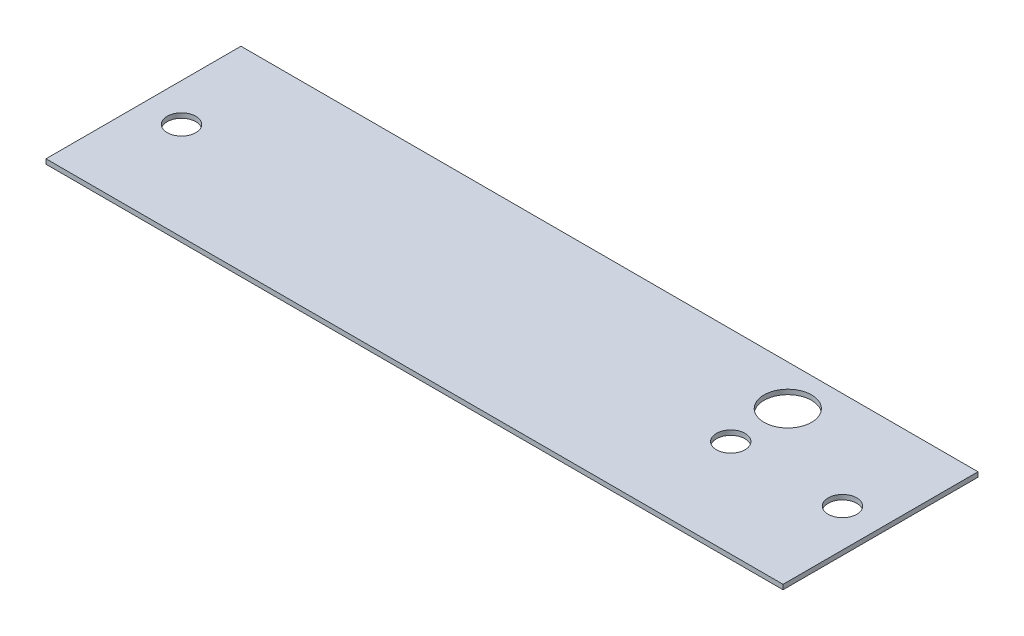
SolidWorks part; units mm, degrees
ref_plane "Front Plane" through (0, 0, 0) normal (0, 0, 1) x (1, 0, 0)
ref_plane "Top Plane" through (0, 0, 0) normal (0, 1, 0) x (1, 0, 0)
ref_plane "Right Plane" through (0, 0, 0) normal (1, 0, 0) x (0, 0, -1)
sketch "Croquis1" plane through (0, 0, 0) normal (0, 1, 0) x (1, 0, 0)
  line L0 (-54.5462, -14.667) -> (22.9538, -35.167) construction
  line L1 (-54.5462, -14.667) -> (22.9538, -14.667)
  line L2 (-54.5462, -14.667) -> (-54.5462, -35.167)
  line L3 (-54.5462, -35.167) -> (22.9538, -35.167)
  line L4 (22.9538, -14.667) -> (22.9538, -35.167)
  line L5 (-15.7962, -8.8925) -> (-15.7962, -42.6636) construction
  line L6 (-68.2053, -24.917) -> (35.6568, -24.917) construction
  circle A0 centre (-50.5462, -24.917) radius 1.5
  circle A1 centre (18.9538, -24.917) radius 1.5
  dimension "D3" = 3
  dimension "D1" = 20.5
  dimension "D2" = 77.5
  dimension "D4" = 69.5
sheet metal parameters "Chapa metálica1" thickness 0.5 parameters "D1"=0.5, "Espesor"=0.5
base flange "Brida base1" sketch "Croquis1" thickness 0.5 reverse thickness direction no parameters "D1"=0.5
sketch "Croquis2" plane through (0, 0, 0) normal (0, 1, 0) x (-1, 0, 0)
  line L0 (-31.9019, 24.917) -> (62.52, 24.917) construction
  line L2 (-7.2038, 3.5874) -> (-7.2038, 47.9899) construction
  line L3 (-22.9538, 35.167) -> (-22.9538, 14.667) construction
  circle A0 centre (-7.2038, 24.917) radius 1.5
  circle A1 centre (-7.2038, 18.917) radius 2.5
  dimension "D1" = 3
  dimension "D4" = 5
  dimension "D2" = 15.75
  dimension "D3" = 6
extrude "Cortar-Extruir1" cut sketch "Croquis2" against normal blind 10 normal cut yes
flat pattern "Chapa desplegada1" [suppressed]
sketch "Líneas de pliegue1" plane through (0, 0, 0) normal (0, 1, 0) x (-1, 0, 0)
sketch3d "Cuadro delimitador1" [suppressed]
  line L0 (77.5, 0, 0) -> (0, 0, 0) construction
  line L1 (77.5, -20.5, 0) -> (0, -20.5, 0) construction
  line L2 (77.5, 0, 0) -> (77.5, -20.5, 0) construction
  line L3 (0, 0, 0) -> (0, -20.5, 0) construction
